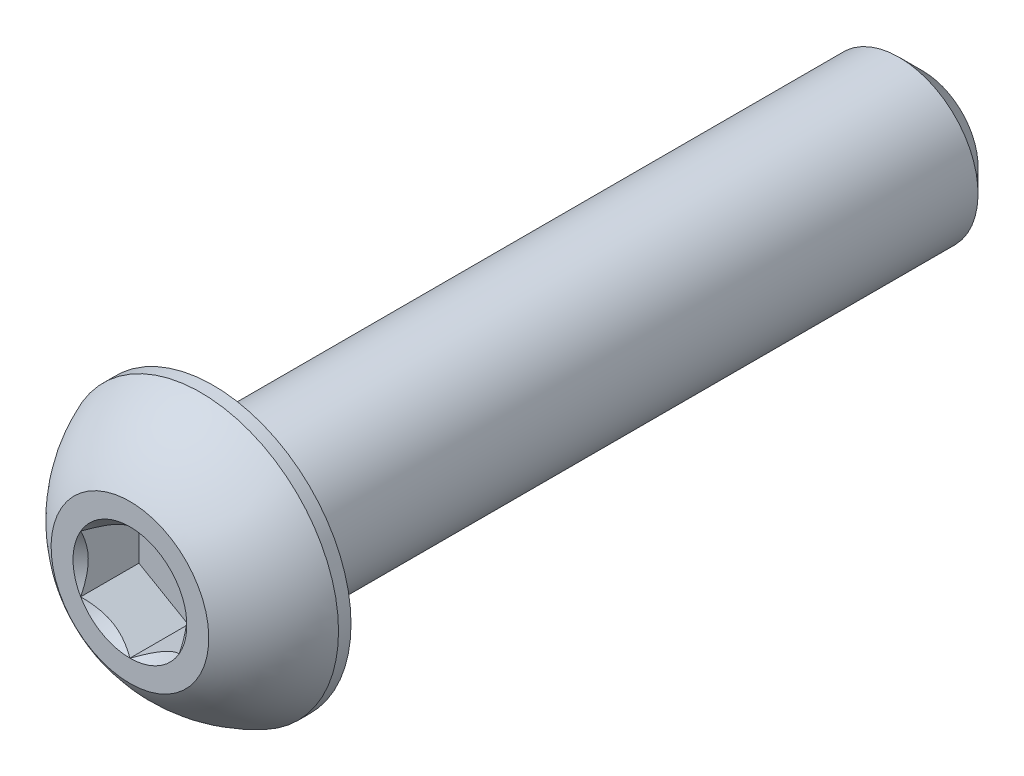
SolidWorks part; units mm, degrees
material "AISI 304"
ref_plane "Front" through (0, 0, 0) normal (0, 0, 1) x (1, 0, 0)
ref_plane "Top" through (0, 0, 0) normal (0, 1, 0) x (1, 0, 0)
ref_plane "Right" through (0, 0, 0) normal (1, 0, 0) x (0, 0, -1)
sketch "Sketch1" plane through (0, 0, 0) normal (1, 0, 0) x (0, 0, -1)
  line L2 (3.3528, 3.175) -> (31.9278, 3.175)
  line L3 (31.9278, 3.175) -> (31.9278, 0)
  line L4 (31.9278, 0) -> (3.3528, 0)
  line L6 (2.8499, 5.5499) -> (3.3528, 5.5499) construction
  line L7 (31.9278, 3.175) -> (31.9278, -3.175) construction
  line L8 (0, 0) -> (3.3528, 0) construction
  line L9 (3.3528, 5.5499) -> (3.3528, -5.5499) construction
  line L11 (3.3528, 3.175) -> (3.3528, 0)
  line L13 (0, 1.9844) -> (0, -1.9844) construction
  line L14 (0, 1.9844) -> (0, 3.175) construction
  arc A3 (0, 3.175) -> (2.8499, 5.5499) centre (5.0603, 0) cw construction
  dimension "D1" = 0.5029
revolve "Revolve1" add sketch "Sketch1" angle 360 mid plane about L4
sketch "Sketch3" plane through (0, 0, -31.9278) normal (0, 0, -1) x (-1, 0, 0)
  circle A0 centre (0, 0) radius 3.175
curve "Helix/Spiral1" pitch 1.27 height 29.845 turns 23.5
sketch "Sketch2" plane through (0, 0, 0) normal (1, 0, 0) x (0, 0, -1)
  line L0 (31.9278, 3.175) -> (33.039, 3.175)
  line L1 (33.039, 3.175) -> (32.5628, 2.3501)
  line L2 (32.5628, 2.3501) -> (32.404, 2.3501)
  line L3 (32.404, 2.3501) -> (31.9278, 3.175)
  line L4 (32.1659, 2.7626) -> (32.8009, 2.7626) construction
  dimension "D1" = 60
  dimension "D2" = 0.1588
  dimension "D3" = 0.635
chamfer "Chamfer1" distance 0.9525 angle 45 1 edges at (0, 3.175, -31.9278)
sweep "Cut-Sweep1" [suppressed] cut profiles "Sketch2" path "Helix/Spiral1"
sketch "Sketch7" plane through (0, 0, 0) normal (1, 0, 0) x (0, 0, -1)
  line L6 (2.8499, 5.5499) -> (3.3528, 5.5499) construction
  line L8 (0, 0) -> (3.3528, 0) construction
  line L11 (3.3528, 5.5499) -> (3.3528, -5.5499) construction
  line L12 (2.8499, 5.5499) -> (3.3528, 5.5499)
  line L13 (0, 0) -> (3.3528, 0)
  line L14 (0, 1.9844) -> (0, -1.9844) construction
  line L15 (3.3528, 5.5499) -> (3.3528, 0)
  line L16 (0, 3.175) -> (0, 0)
  arc A2 (2.8499, 5.5499) -> (0, 3.175) centre (5.0603, 0) ccw construction
  arc A3 (2.8499, 5.5499) -> (0, 3.175) centre (5.0603, 0) ccw
revolve "Revolve2" add sketch "Sketch7" angle 360 mid plane about L13
sketch "Sketch5" plane through (0, 0, 0) normal (0, 0, 1) x (1, 0, 0)
  line L1 (1.9844, -1.1457) -> (1.9844, 1.1457)
  line L2 (1.9844, 1.1457) -> (0, 2.2914)
  line L3 (0, 2.2914) -> (-1.9844, 1.1457)
  line L4 (-1.9844, 1.1457) -> (-1.9844, -1.1457)
  line L5 (-1.9844, -1.1457) -> (0, -2.2914)
  line L6 (0, -2.2914) -> (1.9844, -1.1457)
  circle A0 centre (0, 0) radius 1.9844 construction
extrude "Cut-Extrude2" cut sketch "Sketch5" against normal blind 2.347
sketch "Sketch6" plane through (0, 0, 0) normal (0, 0, 1) x (1, 0, 0)
  circle A0 centre (0, 0) radius 2.2914
extrude "Cut-Extrude3" cut sketch "Sketch6" against normal blind 2.347 draft 45
sketch "Sketch9" [suppressed] plane through (0, 0, -3.3528) normal (0, 0, 1) x (1, 0, 0)
  circle A2 centre (0, 0) radius 3.175
extrude "Boss-Extrude2" [suppressed] add sketch "Sketch9" against normal offset from surface (25.4 mm away) 22.225
sketch "Sketch10" plane through (0, 0, 0) normal (1, 0, 0) x (0, 0, -1)
  line L0 (31.9278, 3.175) -> (31.9278, -3.175) construction
  point P0 (30.0228, -3.175)
  dimension "D1" = 1.905
equation "\"D3@Helix/Spiral1\" = \"Lg@Sketch1\" + \"D4@Helix/Spiral1\""
equation "\"D2@Sketch2\" = \"D4@Helix/Spiral1\" * .125"
equation "\"D3@Sketch2\" = \"D4@Helix/Spiral1\" * .5"
equation "\"D1@Chamfer1\" = \"D4@Helix/Spiral1\" * .75"
equation "\"D1@Cut-Extrude2\" = \"Head Ht@Sketch1\" * .7"
equation "\"D1@Sketch1\" = \"Head Ht@Sketch1\" * .15"
equation "\"D1@Sketch10\" = \"D4@Helix/Spiral1\" * 1.5"
equation "\"D1@Cut-Extrude3\" = \"D1@Cut-Extrude2\""
